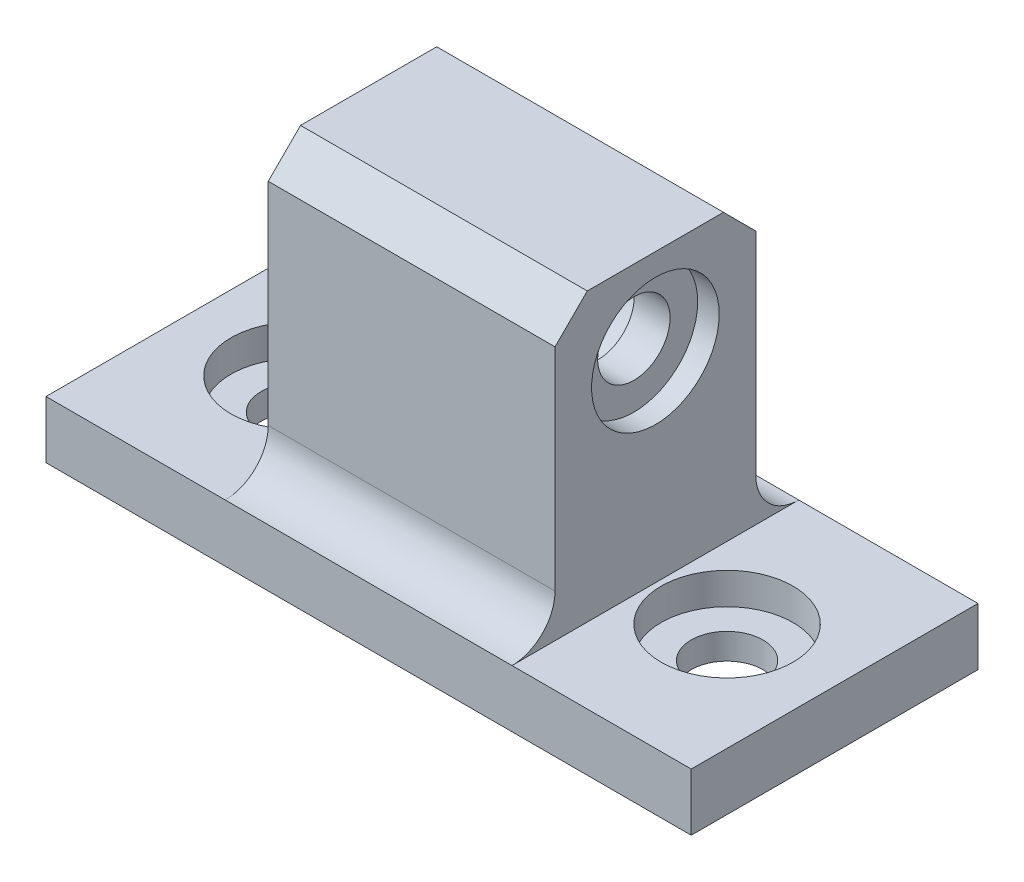
SolidWorks part; units mm, degrees
ref_plane "Front Plane" through (0, 0, 0) normal (0, 0, 1) x (1, 0, 0)
ref_plane "Top Plane" through (0, 0, 0) normal (0, 1, 0) x (1, 0, 0)
ref_plane "Right Plane" through (0, 0, 0) normal (1, 0, 0) x (0, 0, -1)
sketch "Sketch1" plane through (0, 0, 0) normal (0, 1, 0) x (1, 0, 0)
  line L0 (0, 14.1659) -> (0, -12.7898) construction
  line L1 (-22.5, -10) -> (22.5, -10)
  line L2 (-22.5, -10) -> (-22.5, 10)
  line L3 (-22.5, 10) -> (22.5, 10)
  line L4 (22.5, -10) -> (22.5, 10)
  line L5 (-22.5, -10) -> (22.5, 10) construction
  line L6 (-22.5, 10) -> (22.5, -10) construction
  line L7 (10, 7) -> (10, -7)
  line L8 (10, 7) -> (-10, 7)
  line L9 (10, -7) -> (-10, -7)
  line L10 (-10, 7) -> (-10, -7)
  circle A0 centre (15, 0) radius 2.5
  circle A1 centre (15, 0) radius 4.6
  circle A2 centre (-15, 0) radius 2.5
  circle A3 centre (-15, 0) radius 4.6
  point P0 (0, 0)
  point P13 (10, 0)
  point P20 (0, -7)
  point P21 (0, 7)
  dimension "D6" = 9.2
  dimension "D7" = 5
  dimension "D1" = 45
  dimension "D2" = 20
  dimension "D3" = 20
  dimension "D4" = 3
  dimension "D5" = 7.5
extrude "Boss-Extrude1" add sketch "Sketch1" along normal blind 4 contours L1 L4 L3 L2 A1 L10 L8 L7 L9 A3 | A3 A2 | A1 A0 | L8 L10 L9 L7 region at (-22.0076, 0, 0) region at (0, 0, 0) region at (10.5301, 0, 0) region at (-19.4699, 0, 0)
extrude "Boss-Extrude2" add sketch "Sketch1<4>" along normal blind 20 from surface contours L10 L9 L7 L8 starting at face at (0, 4, 0)
sketch "Sketch1<4>" plane through (0, 0, 0) normal (0, 1, 0) x (1, 0, 0) same geometry as "Sketch1"
extrude "Cut-Extrude1" cut sketch "Sketch1<5>" against normal blind 2.2 from surface contours A3 | A1 starting at face at (0, 4, 0)
sketch "Sketch1<5>" plane through (0, 0, 0) normal (0, 1, 0) x (1, 0, 0) same geometry as "Sketch1"
sketch "Sketch2" plane through (10, 0, 0) normal (1, 0, 0) x (0, 0, -1)
  line L0 (-7, 4) -> (7, 4) construction
  circle A0 centre (0, 18) radius 2.525
  circle A1 centre (0, 18) radius 4.6
  circle A2 centre (0, 18) radius 4.45
  dimension "D1" = 9.2
  dimension "D2" = 8.9
  dimension "D3" = 5.05
  dimension "D4" = 14
extrude "Cut-Extrude2" cut sketch "Sketch2" along normal blind 16 from surface contours A1 starting at face at (-10, 14, 0)
extrude "Cut-Extrude3" cut sketch "Sketch2<6>" against normal up to surface (4 mm away) contours A0 region at (10, 18, 0) up to face at (6, 18, 4.6)
sketch "Sketch2<6>" plane through (10, 0, 0) normal (1, 0, 0) x (0, 0, -1) same geometry as "Sketch2"
extrude "Cut-Extrude4" cut sketch "Sketch2<7>" against normal blind 1.5 contours A2 A0 region at (10, 18, 4.3241)
sketch "Sketch2<7>" plane through (10, 0, 0) normal (1, 0, 0) x (0, 0, -1) same geometry as "Sketch2"
fillet "Fillet1" radius 3 2 edges at (0, 4, -7) (0, 4, 7)
chamfer "Chamfer1" distance 2.25 angle 45 2 edges at (0, 24, 7) (0, 24, -7)
ref_axis "Axis1" through (-15, 1.8, 0) along (0, -1, 0)
